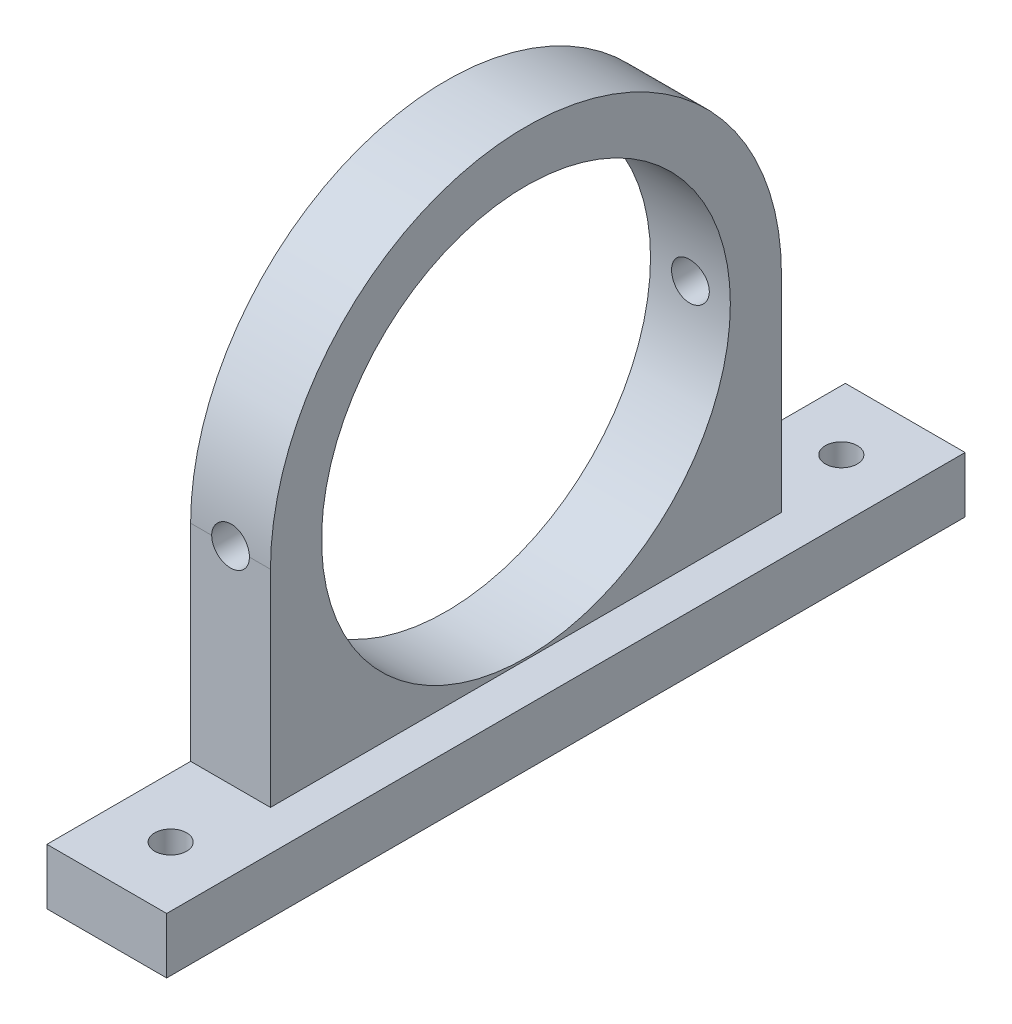
SolidWorks part; units mm, degrees
ref_plane "Front Plane" through (0, 0, 0) normal (0, 0, 1) x (1, 0, 0)
ref_plane "Top Plane" through (0, 0, 0) normal (0, 1, 0) x (1, 0, 0)
ref_plane "Right Plane" through (0, 0, 0) normal (1, 0, 0) x (0, 0, -1)
sketch "Sketch2" plane through (0, 0, 0) normal (1, 0, 0) x (0, 0, -1)
  line L0 (0, 0) -> (-23425.7277, 0) construction
  line L2 (0, -1000) -> (0, 49000) construction
  line L3 (31.75, 0) -> (-31.75, 0)
  line L4 (-31.75, 0) -> (-31.75, 4.445)
  line L5 (-31.75, 4.445) -> (-20.32, 4.445)
  line L6 (-20.32, 4.445) -> (-20.32, 20.85)
  line L7 (20.32, 4.445) -> (20.32, 20.85)
  line L8 (31.75, 0) -> (31.75, 4.445)
  line L9 (31.75, 4.445) -> (20.32, 4.445)
  line L10 (-20.32, 4.445) -> (20.32, 4.445)
  circle A0 centre (0, 20.85) radius 16.256
  arc A1 (-20.32, 20.85) -> (20.32, 20.85) centre (0, 20.85) cw
  point P17 (0, 0)
  dimension "D1" = 32.512
  dimension "D2" = 20.85
  dimension "D3" = 4.445
  dimension "D4" = 20.32
  dimension "D5" = 31.75
extrude "Boss-Extrude1" add sketch "Sketch2" along normal mid plane 6.35 contours L10 L5 L4 L3 L8 L9 | A1 L6 L10 L7 A0 region at (0, 2.2225, 0) region at (0, 4.4998, 0)
sketch "Sketch3" plane through (3.175, 0, 0) normal (1, 0, 0) x (0, 0, -1)
  line L2 (31.75, 0) -> (31.75, 4.445) construction
  line L7 (31.75, 0) -> (-31.75, 0) construction
  line L12 (-31.75, 0) -> (-31.75, 4.445) construction
  line L13 (31.75, 0) -> (31.75, 4.445)
  line L14 (31.75, 0) -> (-31.75, 0)
  line L15 (-31.75, 0) -> (-31.75, 4.445)
  line L16 (-31.75, 4.445) -> (31.75, 4.445)
extrude "Boss-Extrude2" add sketch "Sketch3" along normal blind 3.175
hole_wizard "CSK for #0 Flat Head Machine Screw (100)1" positions "Sketch4" profile "Sketch5" countersink size "#0" standard "ANSI Inch" end condition through all
sketch "Sketch4" plane through (0, 0, -20.32) normal (0, 0, -1) x (-1, 0, 0)
  line L0 (-3.175, 20.85) -> (3.175, 20.85) construction
  point P0 (0, 20.85)
sketch "Sketch5" plane through (0, 20.85, -20.32) normal (1, 0, 0) x (0, 1, 0)
  line L0 (0, 0) -> (0, 52.07)
  line L1 (0, 52.07) -> (1.5, 52.07)
  line L2 (1.5, 52.07) -> (1.5, 0.0095)
  line L3 (1.5, 0.0095) -> (1.5113, 0)
  line L5 (1.5113, 0) -> (0, 0)
  line L6 (-1.5, 0.0095) -> (-1.5113, 0) construction
  line L11 (0, -6.35) -> (0, 107.95) construction
  dimension "Thru Hole Dia." = 3
  dimension "Thru Hole Depth" = 52.07
  dimension "Near C'Sink Dia." = 3.0226
  dimension "Near C'Sink Angle" = 100
sketch "Sketch6" plane through (0, 4.445, 0) normal (0, 1, 0) x (1, 0, 0)
  line L2 (-3.175, -31.75) -> (-3.175, -20.32) construction
  line L4 (6.35, -31.75) -> (-3.175, -31.75) construction
  circle A0 centre (1.5875, -26.67) radius 1.27
  dimension "D1" = 2.54
  dimension "D2" = 4.7625
  dimension "D3" = 5.08
extrude "Cut-Extrude1" cut sketch "Sketch6" against normal blind 6.35
mirror "Mirror2" about plane through (0, 0, 0) normal (0, 0, 1) of "Cut-Extrude1"
